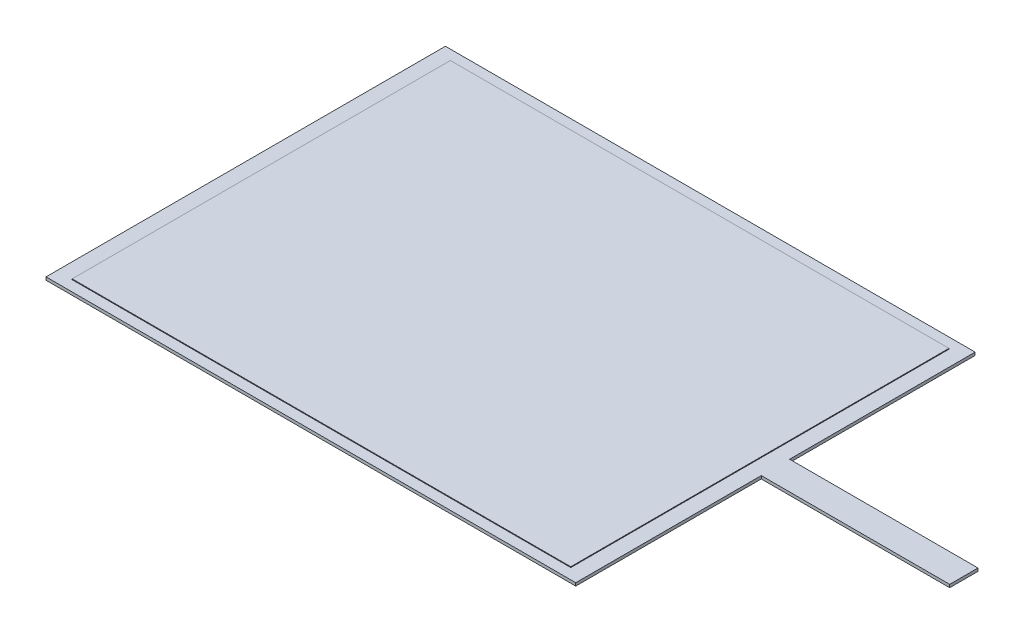
SolidWorks part; units mm, degrees
ref_plane "Front" through (0, 0, 0) normal (0, 0, 1) x (1, 0, 0)
ref_plane "Top" through (0, 0, 0) normal (0, 1, 0) x (1, 0, 0)
ref_plane "Right" through (0, 0, 0) normal (1, 0, 0) x (0, 0, -1)
sketch "Sketch1" plane through (0, 0, 0) normal (0, 1, 0) x (1, 0, 0)
  line L1 (-93.5, -70.5) -> (93.5, -70.5)
  line L2 (-93.5, -70.5) -> (-93.5, 70.5)
  line L3 (-93.5, 70.5) -> (93.5, 70.5)
  line L4 (93.5, -70.5) -> (93.5, 70.5)
  line L5 (-93.5, -70.5) -> (93.5, 70.5) construction
  line L6 (-93.5, 70.5) -> (93.5, -70.5) construction
  line L15 (160, -5) -> (93.5, -5)
  line L16 (160, -5) -> (160, 5)
  line L18 (93.5, -5) -> (93.5, 5)
  line L19 (160, 5) -> (93.5, 5)
  line L20 (160, -5) -> (93.5, 5) construction
  line L21 (93.5, -5) -> (160, 5) construction
  line L22 (-55, 0) -> (55, 0) construction
  line L24 (-88, -66.75) -> (88, -66.75)
  line L25 (-88, -66.75) -> (-88, 66.75)
  line L26 (-88, 66.75) -> (88, 66.75)
  line L27 (88, -66.75) -> (88, 66.75)
  line L28 (-88, -66.75) -> (88, 66.75) construction
  line L29 (-88, 66.75) -> (88, -66.75) construction
  point P0 (0, 0)
  point P6 (0, 0)
  point P9 (126.75, 0)
  point P16 (0, 0)
  point P17 (0, 0)
  point P19 (0, 0)
  point P20 (0, 0)
  point P21 (-93.2676, 70.3026)
  point P23 (0, 0)
  point P27 (0, 0)
  point P28 (93.249, 70.3108)
  point P29 (-93.3062, 70.3538)
  dimension "D1" = 187
  dimension "D2" = 141
  dimension "D3" = 10
  dimension "D4" = 66.5
  dimension "D6" = 176
  dimension "D7" = 133.5
extrude "Boss-Extrude1" add sketch "Sketch1" along normal mid plane 1.04 contours L3 L2 L1 L4 | L16 L19 L4 L15 | L24 L27 L26 L25 region at (-91.158, 0, 0) region at (126.75, 0, 0) region at (0, 0, 0)
extrude "Boss-Extrude2" add sketch "Sketch1<4>" along normal mid plane 1.58 contours L24 L27 L26 L25 region at (0, 0, 0)
sketch "Sketch1<4>" plane through (0, 0, 0) normal (0, 1, 0) x (1, 0, 0) same geometry as "Sketch1"
ref_axis "Axis1" through (0, -0.869, 0) along (0, 1, 0)
